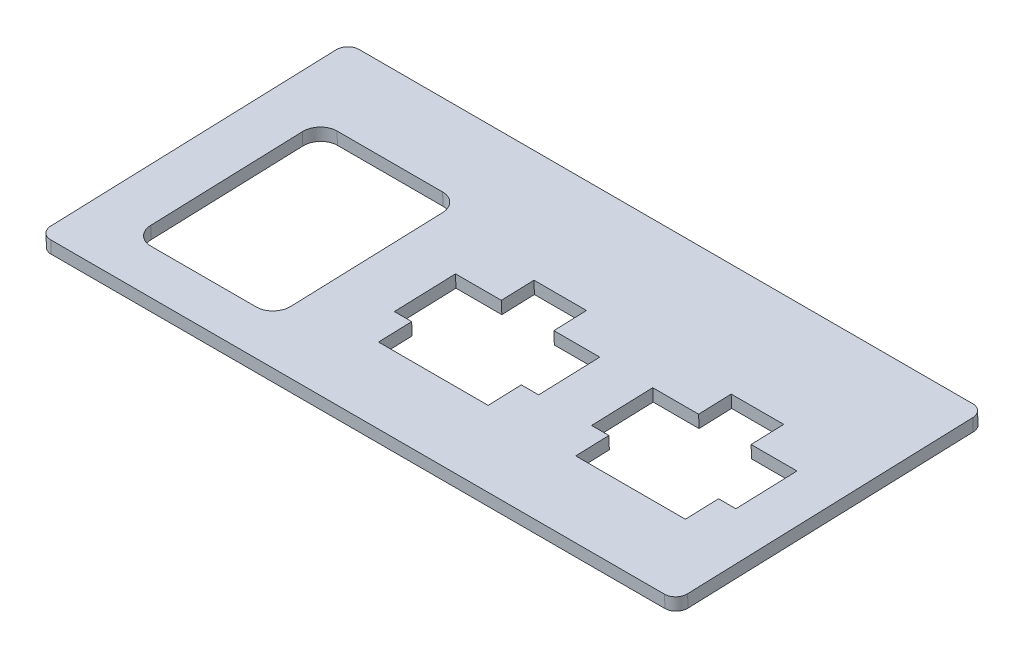
SolidWorks part; units mm, degrees
ref_plane "Front Plane" through (0, 0, 0) normal (0, 0, 1) x (1, 0, 0)
ref_plane "Top Plane" through (0, 0, 0) normal (0, 1, 0) x (1, 0, 0)
ref_plane "Right Plane" through (0, 0, 0) normal (1, 0, 0) x (0, 0, -1)
sketch "Sketch1" plane through (0, -71.9872, -2.5138) normal (0, 0.9994, 0.0349) x (1, 0, 0)
  line L0 (-56.175, 49.6404) -> (56.175, 49.6404) construction
  line L1 (-52.175, -2.9116) -> (-56.175, -2.9116) construction
  line L8 (-55.175, -4.2116) -> (55.175, -4.2116)
  line L9 (55.175, -4.2116) -> (55.175, 49.2404)
  line L10 (55.175, 49.2404) -> (-55.175, 49.2404)
  line L11 (-55.175, 49.2404) -> (-55.175, -4.2116)
  dimension "D4" = 0.4
  dimension "D1" = 1.3
  dimension "D2" = 3.0034
  dimension "D3" = 3.0034
extrude "Boss-Extrude1" add sketch "Sketch1" along normal blind 2.2
sketch "Sketch2" plane through (0, -71.9872, -2.5138) normal (0, -0.9994, -0.0349) x (1, 0, 0)
  line L0 (-4.05, -24.7624) -> (-4.05, -30.4124)
  line L1 (-43.325, -3.2624) -> (-25.025, -3.2624)
  line L2 (-46.325, -6.2624) -> (-46.325, -32.5624)
  line L3 (-43.325, -35.5624) -> (-25.025, -35.5624)
  line L4 (-22.025, -6.2624) -> (-22.025, -32.5624)
  line L5 (-12, -14.1624) -> (-9, -14.1624)
  line L6 (-12, -14.1624) -> (-12, -24.7624)
  line L7 (-12, -24.7624) -> (-4.05, -24.7624)
  line L8 (13, -14.1624) -> (13, -24.7624)
  line L9 (-9, -8.4124) -> (10, -8.4124)
  line L10 (-9, -8.4124) -> (-9, -14.1624)
  line L11 (-4.05, -30.4124) -> (5.05, -30.4124)
  line L12 (10, -8.4124) -> (10, -14.1624)
  line L13 (10, -14.1624) -> (13, -14.1624)
  line L14 (5.05, -24.7624) -> (5.05, -30.4124)
  line L15 (5.05, -24.7624) -> (13, -24.7624)
  line L16 (-13, -5.9124) -> (14, -32.9124) construction
  line L17 (-13, -5.9124) -> (14, -5.9124) construction
  line L18 (-13, -5.9124) -> (-13, -32.9124) construction
  line L19 (-13, -32.9124) -> (14, -32.9124) construction
  line L20 (14, -5.9124) -> (14, -32.9124) construction
  line L21 (17.5875, 3.7502) -> (17.5875, -36.664) construction
  line L22 (47.175, -19.4624) -> (22.175, -19.4624) construction
  line L23 (34.675, -8.4124) -> (34.675, -30.4124) construction
  line L24 (21.175, -5.9124) -> (21.175, -32.9124) construction
  line L25 (48.175, -32.9124) -> (21.175, -32.9124) construction
  line L26 (48.175, -5.9124) -> (48.175, -32.9124) construction
  line L27 (48.175, -5.9124) -> (21.175, -5.9124) construction
  line L28 (-48.175, -19.4124) -> (-46.325, -19.4124) construction
  line L29 (-48.175, -1.4124) -> (-20.175, -1.4124) construction
  line L30 (-48.175, -1.4124) -> (-48.175, -37.4124) construction
  line L31 (-48.175, -37.4124) -> (-20.175, -37.4124) construction
  line L32 (-20.175, -1.4124) -> (-20.175, -37.4124) construction
  line L33 (-34.175, -3.2624) -> (-34.175, -1.4124) construction
  line L34 (0.5, -8.4124) -> (0.5, -30.4124) construction
  line L35 (-12, -19.4624) -> (13, -19.4624) construction
  line L36 (48.175, -5.9124) -> (21.175, -32.9124) construction
  line L37 (30.125, -24.7624) -> (22.175, -24.7624)
  line L38 (30.125, -24.7624) -> (30.125, -30.4124)
  line L39 (25.175, -14.1624) -> (22.175, -14.1624)
  line L40 (25.175, -8.4124) -> (25.175, -14.1624)
  line L41 (39.225, -30.4124) -> (30.125, -30.4124)
  line L42 (44.175, -8.4124) -> (44.175, -14.1624)
  line L43 (44.175, -8.4124) -> (25.175, -8.4124)
  line L44 (22.175, -14.1624) -> (22.175, -24.7624)
  line L45 (47.175, -24.7624) -> (39.225, -24.7624)
  line L46 (47.175, -14.1624) -> (47.175, -24.7624)
  line L47 (47.175, -14.1624) -> (44.175, -14.1624)
  line L48 (39.225, -24.7624) -> (39.225, -30.4124)
  line L49 (21.175, -19.4124) -> (14, -19.4124) construction
  line L51 (48.175, -19.4124) -> (52.175, -19.4124) construction
  line L52 (55.175, 4.2116) -> (55.175, -49.2404) construction
  line L53 (-46.7565, -41.6404) -> (46.7565, -41.6404) construction
  line L54 (-13, -19.4124) -> (-20.175, -19.4124) construction
  line L55 (-34.175, -1.4124) -> (-34.175, 2.8156) construction
  line L56 (-34.175, -37.4124) -> (-34.175, -41.6404) construction
  line L57 (-55.175, -49.2404) -> (-55.175, 4.2116) construction
  line L58 (-48.175, -19.4124) -> (-52.175, -19.4124) construction
  line L59 (-53.075, 2.8156) -> (53.075, 2.8156) construction
  arc A0 (-46.325, -32.5624) -> (-43.325, -35.5624) centre (-43.325, -32.5624) ccw
  arc A1 (-25.025, -35.5624) -> (-22.025, -32.5624) centre (-25.025, -32.5624) ccw
  arc A2 (-25.025, -3.2624) -> (-22.025, -6.2624) centre (-25.025, -6.2624) cw
  arc A3 (-43.325, -3.2624) -> (-46.325, -6.2624) centre (-43.325, -6.2624) ccw
  point P28 (0.5, -19.4124)
  point P63 (34.675, -19.4124)
  dimension "D1" = 3
  dimension "D2" = 32.3
  dimension "D3" = 24.3
  dimension "D4" = 28
  dimension "D5" = 36
  dimension "D6" = 25
  dimension "D7" = 22
  dimension "D8" = 10.6
  dimension "D9" = 19
  dimension "D10" = 9.1
  dimension "D11" = 5.75
  dimension "D12" = 27
  dimension "D13" = 27
  dimension "D14" = 4
  dimension "D15" = 3
  dimension "D16" = 3
extrude "Cut-Extrude1" cut sketch "Sketch2" against normal up to next
fillet "Fillet1" radius 2 4 edges at (-55.175, -71.0348, 1.7336) (55.175, -71.0348, 1.7336) (55.175, -69.1694, -51.6858) (-55.175, -69.1694, -51.6858)
